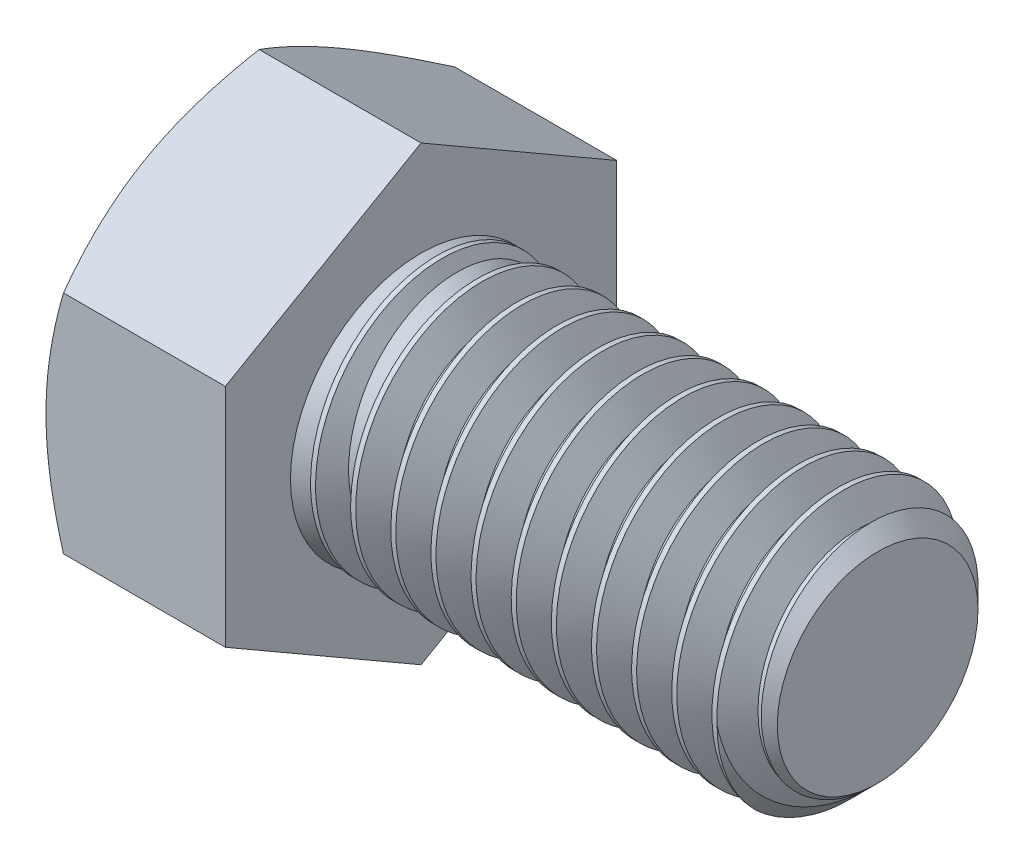
SolidWorks part; units mm, degrees
note: '?' marks a value the reader was unsure of.
ref_plane "Front Plane" through (0, 0, 0) normal (0, 0, 1) x (1, 0, 0)
ref_plane "Top Plane" through (0, 0, 0) normal (0, 1, 0) x (1, 0, 0)
ref_plane "Right Plane" through (0, 0, 0) normal (1, 0, 0) x (0, 0, -1)
sketch "Sketch1" plane through (0, 0, 0) normal (0, 0, 1) x (1, 0, 0)
  line L0 (-15.4781, 0) -> (15.4781, 0) construction
  line L1 (15.4781, 6.35) -> (15.4781, -6.35) construction
  line L2 (-6.7469, 9.525) -> (-6.7469, -9.525) construction
  line L3 (-15.4781, 9.525) -> (-15.4781, -9.525) construction
  line L4 (-7.0009, 6.3562) -> (-6.7469, 6.3562) construction
  line L5 (-6.7469, 6.3562) -> (4.2624, 0) construction
  line L6 (-7.0009, 6.3562) -> (-7.0009, 0) construction
  line L7 (-6.7469, 0) -> (-6.7469, 6.3562) construction
  point P9 (-6.7469, 0)
  point P10 (8.6397, -6.35)
  dimension "Screw Dia" = 12.7
  dimension "Hex" = 19.05
  dimension "Head Ht" = 8.7312
  dimension "Screw Length" = 22.225
  dimension "D1" = 6.8385
  dimension "D2" = 30
  dimension "D3" = 0.254
  dimension "MinThread" = 22.225
  dimension "D4" = 0.0124
ref_plane "Plane2" through (15.4781, 0, 0) normal (1, 0, 0) x (0, 0, -1)
sketch "Sketch5" plane through (15.4781, 0, 0) normal (1, 0, 0) x (0, 0, -1)
  circle A0 centre (0, 0) radius 6.35
extrude "Boss-Extrude3" add sketch "Sketch5" against normal up to vertex (22.225 mm away) up to point (-6.7469, 0, 0)
sketch "Sketch9" plane through (15.4781, 0, 0) normal (1, 0, 0) x (0, 0, -1)
  circle A1 centre (0, 0) radius 6.35
  circle A2 centre (0, 0) radius 6.35
  dimension "D1" = 0
chamfer "Chamfer1" distance 1.4654 angle 45 1 edges at (15.4781, 0, -6.35)
sketch "Sketch6" plane through (-6.7469, 0, 0) normal (-1, 0, 0) x (0, 0, 1)
  line L0 (0, 9.525) -> (0, -9.525) construction
  line L1 (9.525, 5.4993) -> (0, 10.9985)
  line L2 (0, 10.9985) -> (-9.525, 5.4993)
  line L3 (-9.525, 5.4993) -> (-9.525, -5.4993)
  line L4 (-9.525, -5.4993) -> (0, -10.9985)
  line L5 (0, -10.9985) -> (9.525, -5.4993)
  line L6 (9.525, -5.4993) -> (9.525, 5.4993)
  circle A0 centre (0, 0) radius 9.525 construction
extrude "Boss-Extrude4" add sketch "Sketch6" along normal up to vertex (8.7312 mm away) separate body up to point (-15.4781, -9.525, 0)
sketch "Sketch7" plane through (-15.4781, 0, 0) normal (-1, 0, 0) x (0, 0, 1)
  circle A0 centre (0, 0) radius 9.525 construction
  circle A1 centre (0, 0) radius 9.525
sketch "Sketch8" plane through (-15.4781, 0, 0) normal (-1, 0, 0) x (0, 0, 1)
  circle A0 centre (0, 0) radius 9.525 construction
  circle A1 centre (0, 0) radius 9.525
extrude "Cut-Extrude3" cut sketch "Sketch8" against normal through all draft 60 flip side to cut
sketch "Sketch12" plane through (-15.4781, 0, 0) normal (-1, 0, 0) x (0, 0, 1)
  line L0 (0, 7.3342) -> (0, 4.0958) construction
  line L1 (0.2857, 7.3342) -> (0.2858, 4.0958)
  line L2 (-0.2858, 7.3342) -> (-0.2857, 4.0958)
  line L3 (0, 6.35) -> (0, -6.35) construction
  arc A0 (0.2857, 7.3342) -> (-0.2858, 7.3342) centre (0, 7.3342) ccw
  arc A1 (-0.2857, 4.0958) -> (0.2858, 4.0958) centre (0, 4.0958) ccw
  circle A3 centre (0, 0) radius 3.81 construction
  circle A4 centre (0, 0) radius 7.62 construction
  point P2 (0, 5.715)
  dimension "D1" = 7.62
  dimension "D3" = 15.24
  dimension "D2" = 0.5715
extrude "Cut-Extrude4" cut sketch "Sketch12" against normal blind 0.254
pattern_circular "CirPattern1" count 6 over 360 about axis through (0, 0, 0) along (1, 0, 0) of "Cut-Extrude4"
curve "Helix/Spiral1" pitch 1.9538 height 24.1788 turns 12.375 parameters "Pitch"=1.9538
sketch "Sketch10" plane through (0, 0, 0) normal (0, 0, 1) x (1, 0, 0)
  line L0 (15.4781, 6.35) -> (16.2108, 5.0809)
  line L1 (16.2108, 5.0809) -> (16.455, 5.0809)
  line L2 (16.455, 5.0809) -> (17.1877, 6.35)
  line L3 (15.4781, 6.35) -> (17.1877, 6.35)
  line L4 (16.3329, 6.35) -> (16.3329, 5.0809) construction
  line L5 (15.8445, 5.7155) -> (16.8214, 5.7155) construction
  dimension "D1" = 60
  dimension "D2" = 0.2442
  dimension "D3" = 0.9769
sweep "Cut-Sweep1" cut profiles "Sketch10" path "Helix/Spiral1" align with end faces yes
sketch "Sketch13" plane through (0, 0, 0) normal (0, 0, 1) x (1, 0, 0)
  line L0 (-15.4781, 0) -> (15.4781, 0) construction
  line L1 (-6.7469, 6.3562) -> (4.2624, 0) construction
  line L2 (-7.0009, 6.3562) -> (-6.7469, 6.3562) construction
  line L3 (-7.0009, 6.3562) -> (-7.0009, 0) construction
  line L4 (-7.0009, 0) -> (4.2624, 0)
  line L5 (-6.7469, 6.3562) -> (4.2624, 0)
  line L6 (-7.0009, 6.3562) -> (-6.7469, 6.3562)
  line L7 (-7.0009, 6.3562) -> (-7.0009, 0)
revolve "Revolve7" add sketch "Sketch13" angle 360 about L4
ref_axis "Center Axis 1" through (-6.7361, 0, 0) along (1, 0, 0)?
ref_plane "Contact Plane 1" through (-6.7469, 0, 0) normal (1, 0, 0) x (0, 0, -1)
equation "\"D2@Sketch10\" = \"Pitch@Helix/Spiral1\"*.125"
equation "\"D3@Sketch10\" = \"Pitch@Helix/Spiral1\"*.5"
equation "\"D3@Helix/Spiral1\" = \"Screw Length@Sketch1\" + \"Pitch@Helix/Spiral1\""
equation "\"D1@Chamfer1\" = \"Pitch@Helix/Spiral1\"*.75"
equation "\"D1@Sketch12\" = \"Hex@Sketch1\"*.4"
equation "\"D3@Sketch12\" = \"Hex@Sketch1\"*.8"
equation "\"D2@Sketch12\" = \"Hex@Sketch1\"*.03"
equation "\"D1@Sketch1\" = \"Pitch@Helix/Spiral1\"*3.5"
